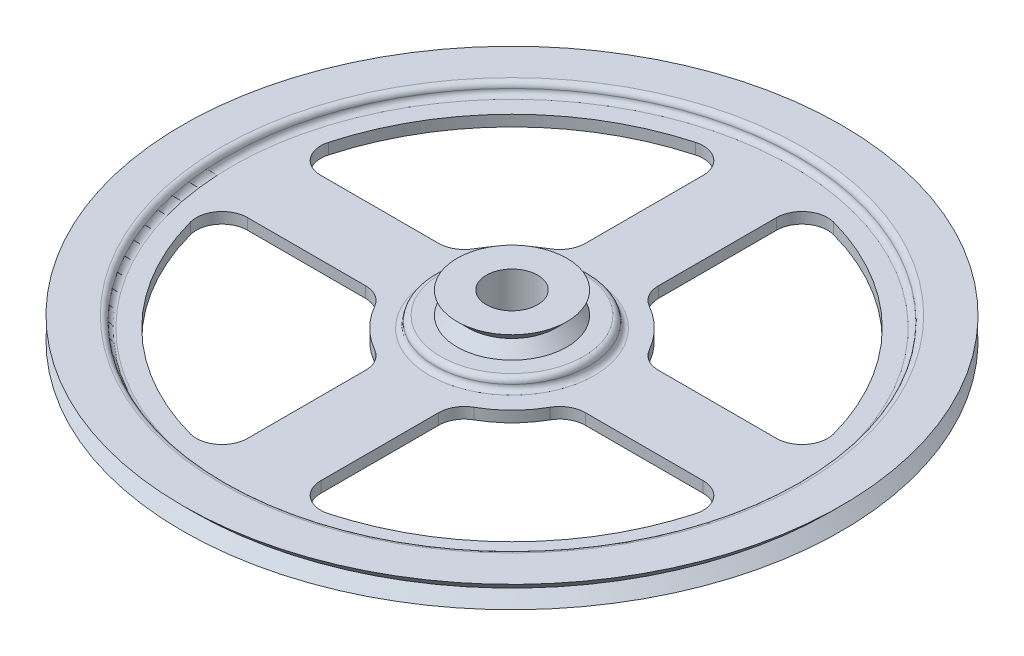
SolidWorks part; units mm, degrees
ref_plane "Front Plane" through (0, 0, 0) normal (0, 0, 1) x (1, 0, 0)
ref_plane "Top Plane" through (0, 0, 0) normal (0, 1, 0) x (1, 0, 0)
ref_plane "Right Plane" through (0, 0, 0) normal (1, 0, 0) x (0, 0, -1)
sketch "Sketch1" plane through (0, 0, 0) normal (0, 0, 1) x (1, 0, 0)
  line L0 (0, 0) -> (0, 13.2622) construction
  line L1 (-3.5, 6) -> (-3.5, 0)
  line L2 (-3.5, 0) -> (-45, 0)
  line L3 (-45, 0) -> (-43.5, 1.5)
  line L4 (-43.5, 1.5) -> (-45, 3)
  line L5 (-45, 3) -> (-7.5, 3)
  line L6 (-7.5, 3) -> (-6, 4.5)
  line L7 (-6, 4.5) -> (-7.5, 6)
  line L8 (-7.5, 6) -> (-3.5, 6)
  dimension "D1" = 3
  dimension "D2" = 7
  dimension "D3" = 15
  dimension "D4" = 90
  dimension "D5" = 45
revolve "Revolve1" add sketch "Sketch1" angle 360 about L0
sketch "Sketch2" plane through (0, 3, 0) normal (0, 1, 0) x (1, 0, 0)
  circle A0 centre (0, 0) radius 10.5
  circle A1 centre (0, 0) radius 39
  circle A2 centre (0, 0) radius 7.5 construction
  circle A3 centre (0, 0) radius 45 construction
  dimension "D1" = 6
  dimension "D2" = 3
extrude "Cut-Extrude1" cut sketch "Sketch2" against normal offset from surface (1.5 mm away) 1.5 up to face at (0, 0, -3.5)
fillet "Fillet1" radius 0.75 4 edges at (0, 3, 10.5) (0, 1.5, 10.5) (0, 3, 39) (0, 1.5, 39)
sketch "Sketch3" plane through (0, 1.5, 0) normal (0, 1, 0) x (1, 0, 0)
  line L0 (35.3986, -5) -> (12.8087, -5)
  line L1 (53.196, 0) -> (-55.1219, 0) construction
  line L3 (0, -47.9172) -> (0, 58.1929) construction
  line L4 (5, -12.8087) -> (5, -35.3986)
  line L6 (-5, -35.3986) -> (-5, -12.8087)
  line L8 (-12.8087, -5) -> (-35.3986, -5)
  line L10 (-35.3986, 5) -> (-12.8087, 5)
  line L12 (-5, 12.8087) -> (-5, 35.3986)
  line L14 (5, 35.3986) -> (5, 12.8087)
  line L16 (12.8087, 5) -> (35.3986, 5)
  arc A0 (35.3986, 5) -> (5, 35.3986) centre (0, 0) ccw
  arc A1 (12.8087, 5) -> (5, 12.8087) centre (0, 0) ccw
  arc A2 (5, -12.8087) -> (12.8087, -5) centre (0, 0) ccw
  arc A3 (5, -35.3986) -> (35.3986, -5) centre (0, 0) ccw
  arc A4 (-35.3986, -5) -> (-5, -35.3986) centre (0, 0) ccw
  arc A5 (-5, 35.3986) -> (-35.3986, 5) centre (0, 0) ccw
  arc A6 (-5, 12.8087) -> (-12.8087, 5) centre (0, 0) ccw
  arc A7 (-12.8087, -5) -> (-5, -12.8087) centre (0, 0) ccw
  circle A8 centre (0, 0) radius 38.25 construction
  circle A9 centre (0, 0) radius 11.25 construction
  point P25 (0, 0)
  point P26 (0, 0)
  point P27 (0, 0)
  point P28 (0, 0)
  point P29 (0, 0)
  point P30 (0, 0)
  point P31 (0, 0)
  point P32 (0, 0)
  point P33 (0, 0)
  point P34 (0, 0)
  point P35 (0, 0)
  point P36 (0, 0)
  point P37 (0, 0)
  point P38 (0, 0)
  point P39 (0, 0)
  point P40 (0, 0)
  point P43 (0, 0)
  point P44 (53.196, 0)
  point P45 (-55.1219, 0)
  point P46 (0, -47.9172)
  point P47 (0, 58.1929)
  dimension "D2" = 2.5
  dimension "D3" = 2.5
  dimension "D1" = 5
extrude "Cut-Extrude2" cut sketch "Sketch3" against normal up to surface (1.5 mm away) up to face at (0, 0, -3.5)
fillet "Fillet2" radius 3.5 16 edges at (35.3986, 0.75, 5) (35.3986, 0.75, -5) (5, 0.75, -35.3986) (-5, 0.75, -35.3986) (-35.3986, 0.75, -5) (-12.8087, 0.75, -5) (-5, 0.75, -12.8087) (5, 0.75, -12.8087) (12.8087, 0.75, -5) (12.8087, 0.75, 5) (5, 0.75, 12.8087) (5, 0.75, 35.3986) (-5, 0.75, 35.3986) (-5, 0.75, 12.8087) (-12.8087, 0.75, 5) (-35.3986, 0.75, 5)
